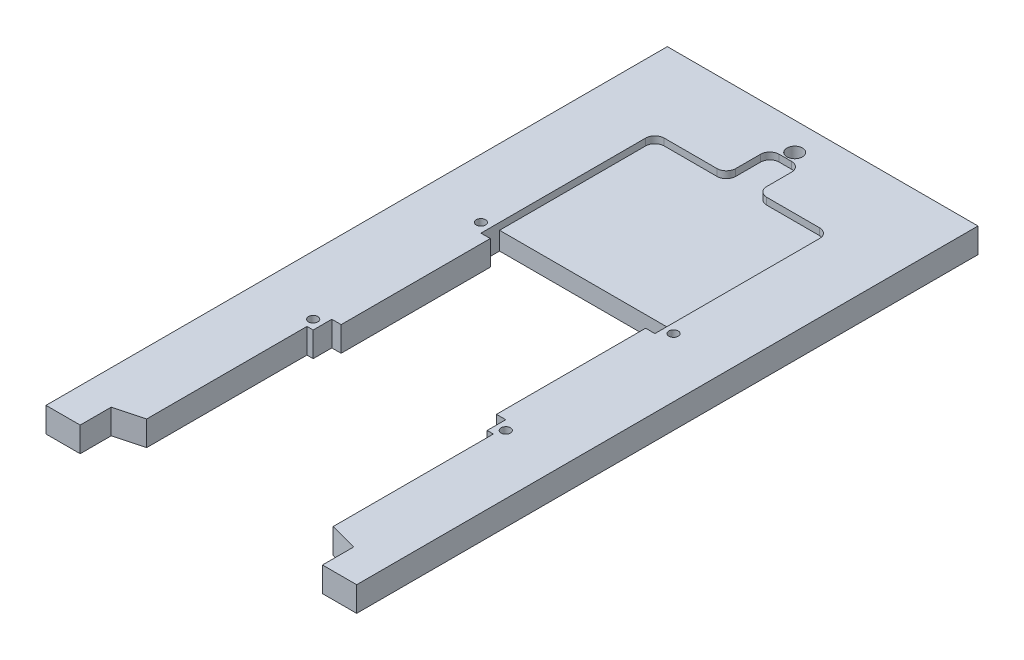
SolidWorks part; units mm, degrees
ref_plane "Front Plane" through (0, 0, 0) normal (0, 0, 1) x (1, 0, 0)
ref_plane "Top Plane" through (0, 0, 0) normal (0, 1, 0) x (1, 0, 0)
ref_plane "Right Plane" through (0, 0, 0) normal (1, 0, 0) x (0, 0, -1)
sketch "Sketch1" plane through (0, 0, 0) normal (0, 1, 0) x (1, 0, 0)
  line L1 (-30, 12.4115) -> (-30, 64)
  line L2 (-28, 124) -> (28, 124)
  line L3 (30, 64) -> (30, 12.4115)
  line L6 (-50, 0) -> (-39, 0)
  line L8 (-28, 70) -> (-28, 64)
  line L9 (-28, 64) -> (-30, 64)
  line L10 (28, 70) -> (28, 64)
  line L11 (28, 64) -> (30, 64)
  line L12 (-28, 70) -> (-25, 70)
  line L13 (-25, 70) -> (-25, 118)
  line L14 (-25, 118) -> (-28, 118)
  line L15 (-28, 118) -> (-28, 124)
  line L16 (28, 124) -> (28, 118)
  line L17 (28, 118) -> (25, 118)
  line L18 (25, 118) -> (25, 70)
  line L19 (25, 70) -> (28, 70)
  line L20 (-39, 0) -> (-39, 10)
  line L21 (-39, 10) -> (-30, 12.4115)
  line L22 (39, 0) -> (39, 10)
  line L23 (39, 10) -> (30, 12.4115)
  line L24 (-50, 0) -> (-50, 200)
  line L25 (-50, 200) -> (50, 200)
  line L26 (50, 200) -> (50, 0)
  line L27 (50, 0) -> (39, 0)
  circle A0 centre (-31, 67) radius 1.5
  circle A1 centre (31, 67) radius 1.5
  circle A2 centre (-31, 121) radius 1.5
  circle A3 centre (31, 121) radius 1.5
  dimension "D17" = 3
  dimension "D2" = 60
  dimension "D3" = 67
  dimension "D5" = 60
  dimension "D6" = 56
  dimension "D7" = 6
  dimension "D8" = 3
  dimension "D9" = 78
  dimension "D10" = 10
  dimension "D11" = 105
  dimension "D12" = 100
  dimension "D13" = 200
  dimension "D14" = 50
  dimension "D16" = 62
  dimension "D18" = 54
  dimension "D19" = 3
  dimension "D20" = 3
extrude "Boss-Extrude1" add sketch "Sketch1" along normal blind 8
sketch "Sketch2" plane through (0, 8, 0) normal (0, 1, 0) x (1, 0, 0)
  line L1 (-28, 124) -> (28, 124)
  line L2 (-28, 124) -> (-28, 174)
  line L3 (-28, 174) -> (28, 174)
  line L4 (28, 124) -> (28, 174)
  dimension "D1" = 50
extrude "Cut-Extrude1" cut sketch "Sketch2" against normal blind 2.2
sketch "Sketch3" plane through (0, 8, 0) normal (0, 1, 0) x (1, 0, 0)
  line L0 (28, 174) -> (-28, 174) construction
  line L1 (-5, 174) -> (5, 174)
  line L2 (-5, 174) -> (-5, 188)
  line L3 (-5, 188) -> (5, 188)
  line L4 (5, 174) -> (5, 188)
  line L5 (-28, 174) -> (-28, 124) construction
  dimension "D1" = 10
  dimension "D2" = 23
  dimension "D3" = 14
extrude "Cut-Extrude2" cut sketch "Sketch3" against normal up to surface (2.2 mm away) up to face at (0, 5.8, -149)
sketch "Sketch4" plane through (0, 8, 0) normal (0, 1, 0) x (1, 0, 0)
  line L0 (-5, 174) -> (-28, 174) construction
  circle A0 centre (0, 191) radius 2.5
  dimension "D1" = 5
  dimension "D2" = 17
extrude "Cut-Extrude3" cut sketch "Sketch4" against normal up to next
fillet "Fillet1" radius 3 6 edges at (28, 6.9, -174) (-28, 6.9, -174) (5, 6.9, -174) (-5, 6.9, -174) (5, 6.9, -188) (-5, 6.9, -188)
sketch "Sketch5" plane through (0, 0, 0) normal (0, -1, 0) x (1, 0, 0)
  circle A0 centre (-31, -67) radius 2.75
  circle A1 centre (31, -67) radius 2.75
  circle A2 centre (-31, -121) radius 2.75
  circle A3 centre (31, -121) radius 2.75
  dimension "D1" = 5.5
extrude "Cut-Extrude4" cut sketch "Sketch5" against normal blind 3
chamfer "Chamfer1" distance 1.25 angle 40 4 edges at (31, 3, -68.5) (31, 3, -122.5) (-31, 3, -122.5) (-31, 3, -68.5) first distance on face at (31, 3, -68.5) first distance on face at (31, 3, -122.5) first distance on face at (-31, 3, -122.5) first distance on face at (-31, 3, -68.5)
